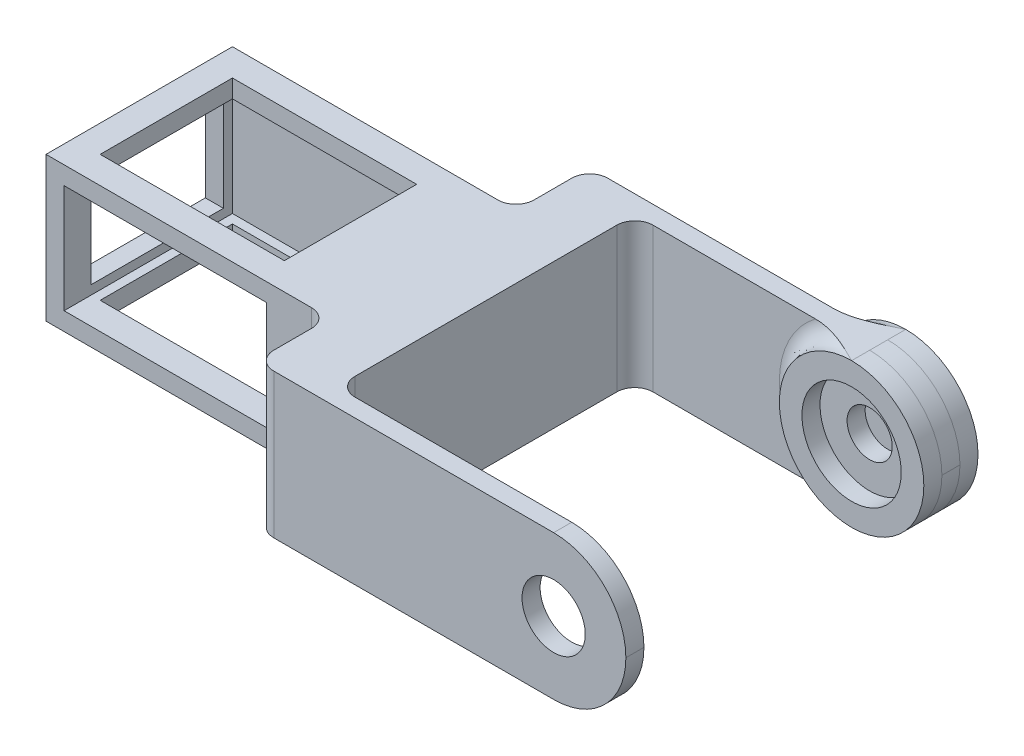
SolidWorks part; units mm, degrees
ref_plane "Front Plane" through (0, 0, 0) normal (0, 0, 1) x (1, 0, 0)
ref_plane "Top Plane" through (0, 0, 0) normal (0, 1, 0) x (1, 0, 0)
ref_plane "Right Plane" through (0, 0, 0) normal (1, 0, 0) x (0, 0, -1)
sketch "Sketch1" plane through (0, 0, 0) normal (0, 0, 1) x (1, 0, 0)
  line L1 (-13.2, 8) -> (13.2, 8)
  line L2 (-13.2, 8) -> (-13.2, -8)
  line L3 (-13.2, -8) -> (13.2, -8)
  line L4 (13.2, 8) -> (13.2, -8)
  line L5 (-13.2, 8) -> (13.2, -8) construction
  line L6 (-13.2, -8) -> (13.2, 8) construction
  point P0 (0, 0)
  dimension "D1" = 26.4
  dimension "D2" = 16
extrude "Boss-Extrude1" add sketch "Sketch1" along normal blind 20.65
sketch "Sketch2" plane through (0, 0, 20.65) normal (0, 0, 1) x (1, 0, 0)
  line L1 (-11.2, 6) -> (11.2, 6)
  line L2 (-11.2, 6) -> (-11.2, -6)
  line L3 (-11.2, -6) -> (11.2, -6)
  line L4 (11.2, 6) -> (11.2, -6)
  line L5 (-11.2, 6) -> (11.2, -6) construction
  line L6 (-11.2, -6) -> (11.2, 6) construction
  point P0 (0, 0)
  dimension "D1" = 22.4
  dimension "D2" = 12
extrude "Cut-Extrude1" cut sketch "Sketch2" against normal blind 18.65
sketch "Sketch3" plane through (0, 8, 0) normal (0, 1, 0) x (1, 0, 0)
  line L0 (10.2, -17.65) -> (-10.2, -3) construction
  line L1 (10.2, -17.65) -> (-10.2, -17.65)
  line L2 (10.2, -17.65) -> (10.2, -3)
  line L3 (10.2, -3) -> (-10.2, -3)
  line L4 (-10.2, -17.65) -> (-10.2, -3)
  line L5 (-10.2, -17.65) -> (10.2, -3) construction
  line L6 (13.2, -20.65) -> (-13.2, 0) construction
  line L7 (13.2, 0) -> (-13.2, -20.65) construction
  line L8 (13.2, -20.65) -> (13.2, 0) construction
  line L9 (13.2, -20.65) -> (-13.2, -20.65) construction
  point P12 (0, -10.325)
  point P13 (0, -10.325)
  dimension "D1" = 3
  dimension "D2" = 3
extrude "Cut-Extrude2" cut sketch "Sketch3" against normal blind 38.65
sketch "Sketch4" plane through (-13.2, 0, 0) normal (-1, 0, 0) x (0, 0, 1)
  line L0 (20.65, -8) -> (0, -8) construction
  line L1 (20.65, 8) -> (17.65, 8)
  line L2 (20.65, 8) -> (20.65, -8)
  line L3 (20.65, -8) -> (17.65, -8)
  line L4 (17.65, 8) -> (17.65, -8)
  line L5 (0, -8) -> (20.65, 8) construction
  line L6 (0, 8) -> (20.65, -8) construction
  line L7 (20.65, 8) -> (0, 8) construction
  line L8 (3, 5) -> (17.65, 5)
  line L9 (3, 5) -> (3, -5)
  line L10 (3, -5) -> (17.65, -5)
  line L11 (17.65, 5) -> (17.65, -5)
  line L12 (3, 5) -> (17.65, -5) construction
  line L13 (3, -5) -> (17.65, 5) construction
  line L14 (0, 8) -> (0, -8) construction
  point P10 (10.325, 0)
  dimension "D1" = 3
  dimension "D2" = 3
  dimension "D3" = 3
extrude "Cut-Extrude4" cut sketch "Sketch4" against normal blind 7 contours L9 L10 L4 L8
sketch "Sketch7" plane through (13.2, 0, 0) normal (1, 0, 0) x (0, 0, -1)
  line L0 (-10.325, -8) -> (-10.325, 8) construction
  line L1 (-20.65, -8) -> (0, -8) construction
  line L2 (-20.65, 8) -> (0, 8) construction
  line L4 (-28.825, -8) -> (8.175, -8)
  line L5 (-28.825, -8) -> (-28.825, 8)
  line L6 (-28.825, 8) -> (8.175, 8)
  line L7 (8.175, -8) -> (8.175, 8)
  line L8 (-28.825, -8) -> (8.175, 8) construction
  line L9 (-28.825, 8) -> (8.175, -8) construction
  point P6 (-10.325, 0)
  dimension "D1" = 37
extrude "Boss-Extrude4" add sketch "Sketch7" along normal blind 41 from offset 5 separate body
sketch "Sketch8" plane through (13.2, 0, 0) normal (1, 0, 0) x (0, 0, -1)
  line L1 (-20.65, -8) -> (0, -8)
  line L2 (-20.65, -8) -> (-20.65, 8)
  line L3 (-20.65, 8) -> (0, 8)
  line L4 (0, -8) -> (0, 8)
extrude "Boss-Extrude5" add sketch "Sketch8" along normal blind 5
sketch "Sketch9" plane through (0, 0, 20.65) normal (0, 0, 1) x (1, 0, 0)
  line L0 (11.2, 0) -> (18.2, 0) construction
  line L1 (11.2, -6) -> (11.2, 6) construction
  line L2 (18.2, 8) -> (18.2, -8) construction
  line L3 (18.2, 8) -> (-13.2, 8) construction
  line L4 (16.2, 6) -> (13.2, 6)
  line L5 (16.2, 6) -> (16.2, -6)
  line L6 (16.2, -6) -> (13.2, -6)
  line L7 (13.2, 6) -> (13.2, -6)
  line L8 (16.2, 6) -> (13.2, -6) construction
  line L9 (16.2, -6) -> (13.2, 6) construction
  circle A0 centre (13.95, 0) radius 1.05
  point P6 (14.7, 0)
  dimension "D3" = 2.75
  dimension "D1" = 2
  dimension "D2" = 2
extrude "Cut-Extrude6" cut sketch "Sketch9" against normal blind 15 contours L7 A0 | L7 A0
sketch "Sketch10" plane through (59.2, 0, 0) normal (1, 0, 0) x (0, 0, -1)
  line L0 (-28.825, 8) -> (-28.825, -8) construction
  line L1 (-26.825, 17.1345) -> (6.175, 17.1345)
  line L2 (-26.825, 17.1345) -> (-26.825, -22.6454)
  line L3 (-26.825, -22.6454) -> (6.175, -22.6454)
  line L4 (6.175, 17.1345) -> (6.175, -22.6454)
  line L5 (8.175, -8) -> (8.175, 8) construction
  dimension "D1" = 2
  dimension "D2" = 2
extrude "Cut-Extrude7" cut sketch "Sketch10" against normal blind 34
fillet "Fillet1" radius 8 2 edges at (59.2, -8, 27.825) (59.2, 8, 27.825)
sketch "Sketch14" plane through (0, 0, 26.825) normal (0, 0, -1) x (-1, 0, 0)
  circle A0 centre (-51.2, 0) radius 8
  dimension "D1" = 16
extrude "Boss-Extrude7" add sketch "Sketch14" along normal blind 2 and the other way blind 4 from offset 35
sketch "Sketch15" plane through (0, 0, -10.175) normal (0, 0, -1) x (-1, 0, 0)
  circle A0 centre (-51.2, 0) radius 5.5
  circle A1 centre (-51.2, 0) radius 8 construction
  dimension "D1" = 11
extrude "Cut-Extrude11" cut sketch "Sketch15" along normal blind 6 from offset 10 offset against normal yes
sketch "Sketch16" plane through (0, 0, 0) normal (0, 0, -1) x (-1, 0, 0)
  line L0 (13.2, 8) -> (13.2, -8) construction
  line L1 (-18.2, 8) -> (13.2, 8) construction
  circle A0 centre (5.2, 0) radius 5
  dimension "D1" = 8
  dimension "D3" = 10
  dimension "D2" = 8
extrude "Boss-Extrude8" add sketch "Sketch16" along normal blind 2
sketch "Sketch17" plane through (0, 0, -6.175) normal (0, 0, 1) x (1, 0, 0)
  circle A0 centre (51.2, 0) radius 2.5
  circle A1 centre (51.2, 0) radius 5.5 construction
  dimension "D1" = 5
extrude "Cut-Extrude12" cut sketch "Sketch17" against normal blind 2 and the other way blind 54
sketch "Sketch18" plane through (0, 0, -2) normal (0, 0, -1) x (-1, 0, 0)
  circle A0 centre (5.2, 0) radius 2.25
  circle A1 centre (5.2, 0) radius 5 construction
  dimension "D1" = 4.5
extrude "Boss-Extrude9" add sketch "Sketch18" along normal blind 2
fillet "Fillet2" radius 8 2 edges at (59.2, -8, -7.175) (59.2, 8, -7.175)
sketch "Sketch19" plane through (0, 0, -8.175) normal (0, 0, -1) x (-1, 0, 0)
  circle A0 centre (-51.2, 0) radius 3.5
  dimension "D1" = 7
extrude "Cut-Extrude13" cut sketch "Sketch19" against normal blind 24 from offset 30 offset against normal yes
fillet "Fillet3" radius 2 4 edges at (18.2, 0, 20.65) (18.2, 0, 0) (25.2, 0, 26.825) (25.2, 0, -6.175)
fillet "Fillet4" radius 2 2 edges at (18.2, 0, 28.825) (18.2, 0, -8.175)
fillet "Fillet5" radius 2 1 edges at (43.2, 0, -8.175)
fillet "Fillet6" radius 2 1 edges at (43.2, 0, -6.175)
equation "\"Servo_Length\"= 22.4"
equation "\"Servo_Width\"= 12"
equation "\"Servo_Hight\"= 18.65"
equation "\"Servo_CLEARANCE\"= 0.5"
equation "\"Wall_Thickness\"= 2"
equation "\"D1@Sketch1\"=\"Servo_Length\"+2*(\"Wall_Thickness\")"
equation "\"D2@Sketch1\"=\"Servo_Width\"+2*(\"Wall_Thickness\")"
equation "\"D1@Boss-Extrude1\"=\"Servo_Hight\"+\"Wall_Thickness\""
equation "\"D1@Sketch2\"=\"Servo_Length\""
equation "\"D2@Sketch2\"=\"Servo_Width\""
equation "\"D1@Cut-Extrude1\"=\"Servo_Hight\""
